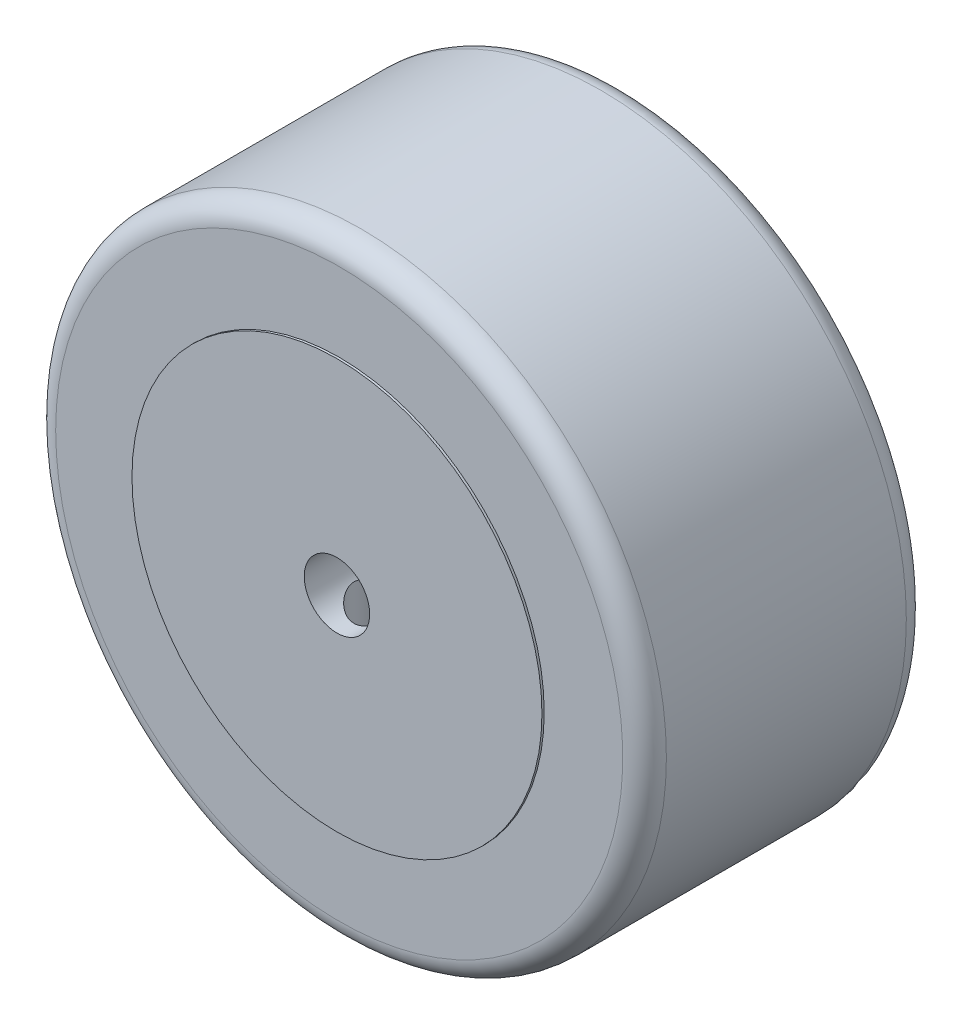
SolidWorks part; units mm, degrees
ref_plane "Front" through (0, 0, 0) normal (0, 0, 1) x (1, 0, 0)
ref_plane "Top" through (0, 0, 0) normal (0, 1, 0) x (1, 0, 0)
ref_plane "Right" through (0, 0, 0) normal (1, 0, 0) x (0, 0, -1)
ref_axis "X" through (-80.9, 0, 0) along (1, 0, 0)
ref_axis "Y" through (0, -50, 0) along (0, 1, 0)
ref_axis "Z" through (0, 0, -80.9) along (0, 0, 1)
sketch "Sketch1" plane through (0, 0, 0) normal (1, 0, 0) x (0, 0, -1)
  line L0 (0, 0) -> (0, 9.398)
  line L1 (0, 9.398) -> (1.524, 9.398)
  line L2 (1.524, 9.398) -> (1.524, 8.382)
  line L3 (1.524, 8.382) -> (5.842, 8.382)
  line L4 (5.842, 8.382) -> (5.842, 10.16)
  line L5 (5.842, 10.16) -> (7.366, 10.16)
  line L6 (7.366, 10.16) -> (7.366, 8.382)
  line L7 (7.366, 8.382) -> (11.684, 8.382)
  line L8 (11.684, 8.382) -> (11.684, 9.398)
  line L9 (11.684, 9.398) -> (13.208, 9.398)
  line L10 (13.208, 9.398) -> (13.208, 7.493)
  line L11 (4.318, 0) -> (0, 0)
  line L12 (4.318, 0) -> (4.318, 7.493)
  line L13 (4.318, 7.493) -> (13.208, 7.493)
  line L14 (13.7764, 0) -> (-13.7764, 0) construction
  dimension "D1" = 13.208
  dimension "D2" = 8.89
  dimension "D3" = 14.986
  dimension "D4" = 20.32
  dimension "D5" = 1.524
  dimension "D6" = 16.764
  dimension "D7" = 18.796
revolve "Revolve1" add sketch "Sketch1" angle 360 about L14
hole_wizard "Ø3.0 (3) Diameter Hole1" positions "Sketch2" profile "Sketch3" hole size "Ø3.0" standard "ANSI Metric" end condition up to next
sketch "Sketch2" plane through (0, 0, 0) normal (0, 0, 1) x (1, 0, 0)
  point P0 (0, 0)
sketch "Sketch3" plane through (0, 0, 0) normal (1, 0, 0) x (0, -1, 0)
  line L0 (0, 0) -> (0, 4.318)
  line L1 (0, 4.318) -> (1.5, 4.318)
  line L2 (1.5, 4.318) -> (1.5, 0)
  line L5 (1.5, 0) -> (0, 0)
  line L11 (0, -6.35) -> (0, 107.95) construction
  dimension "Thru Hole Dia." = 3
  dimension "Thru Hole Depth" = 4.318
sketch "Sketch5" plane through (0, 0, 0) normal (1, 0, 0) x (0, 0, -1)
  line L0 (1.104, 14) -> (12.104, 14)
  line L1 (13.104, 13) -> (13.104, 8)
  line L2 (13.104, 8) -> (0.104, 8)
  line L3 (0.104, 8) -> (0.104, 13)
  line L4 (0, 0) -> (26.3689, 0) construction
  line L5 (0, 9.398) -> (0, -9.398) construction
  line L7 (6.604, 14) -> (6.604, 10.16) construction
  line L8 (7.366, 10.16) -> (5.842, 10.16) construction
  arc A0 (12.104, 14) -> (13.104, 13) centre (12.104, 13) cw
  arc A1 (0.104, 13) -> (1.104, 14) centre (1.104, 13) cw
  dimension "D2" = 1
  dimension "D1" = 13
  dimension "D3" = 28
  dimension "D4" = 16
revolve "Revolve2" add sketch "Sketch5" angle 360 about axis through (0, 0, -80.9) along (0, 0, 1)
hole_wizard "#4-40 Tapped Hole1" positions "3DSketch1" profile "Sketch4" tap size "#4-40" standard "ANSI Inch" end condition through all
sketch3d "3DSketch1"
  line L0 (0, 9.398, -1.905) -> (0, 9.398, 0) construction
  line L2 (0, 0, 0) -> (0, 9.398, 0) construction
  circle A0 centre (0, 0, 0) radius 9.398 construction
  point P0 (0, 9.398, -1.905)
  point P7 (0, 0, -9.398)
  dimension "D1" = 1.905
sketch "Sketch4" plane through (0, 9.398, -1.905) normal (1, 0, 0) x (0, 0, 1)
  line L0 (0, 0) -> (0, 23.398)
  line L1 (0, 23.398) -> (1.1303, 23.398)
  line L2 (1.1303, 23.398) -> (1.1303, 0)
  line L5 (1.1303, 0) -> (0, 0)
  line L11 (0, -6.35) -> (0, 107.95) construction
  dimension "Thru Tap Drill Dia." = 2.2606
  dimension "Thru Tap Drill Depth" = 23.398
cosmetic thread "Hole Thread3" parameters "D2"=2.8448
